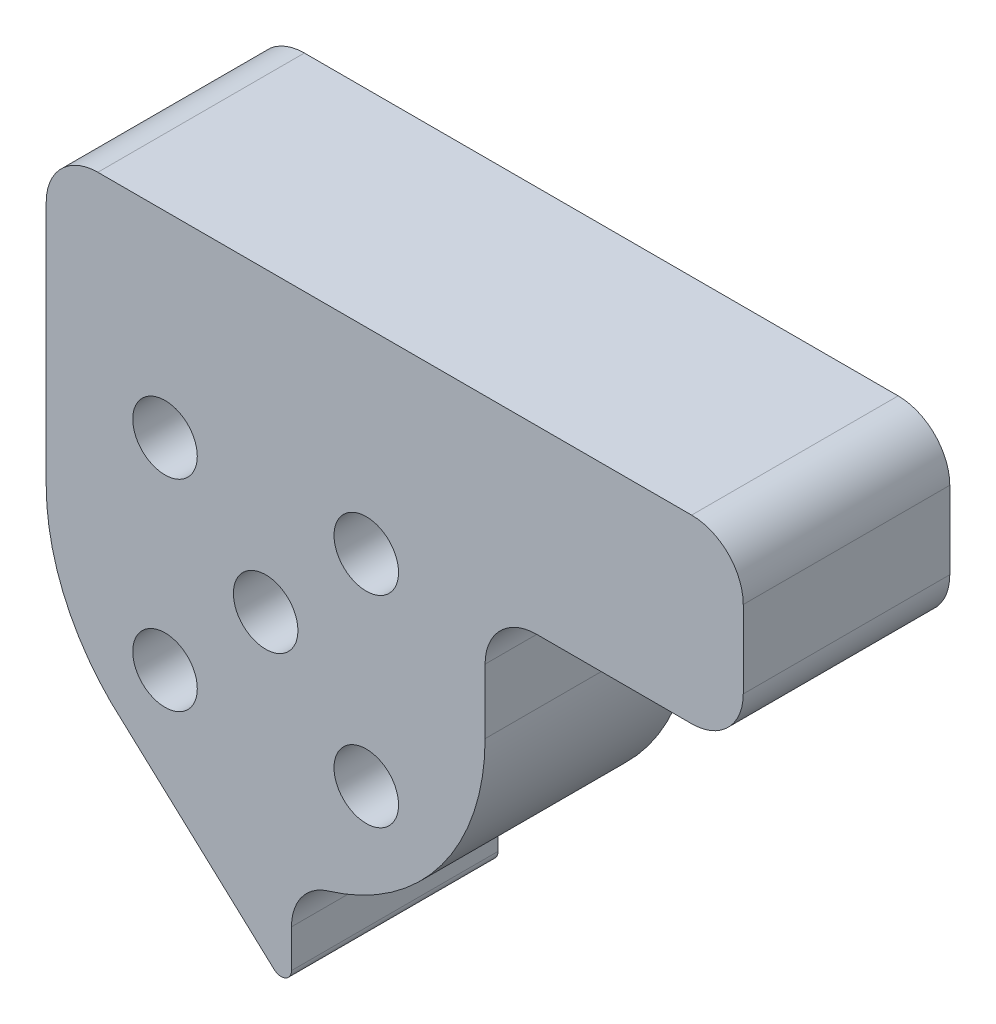
SolidWorks part; units mm, degrees
ref_plane "Front Plane" through (0, 0, 0) normal (0, 0, 1) x (1, 0, 0)
ref_plane "Top Plane" through (0, 0, 0) normal (0, 1, 0) x (1, 0, 0)
ref_plane "Right Plane" through (0, 0, 0) normal (1, 0, 0) x (0, 0, -1)
sketch "Sketch1" plane through (0, 0, 0) normal (0, 0, 1) x (1, 0, 0)
  line L0 (10.795, 0) -> (10.795, 5.715)
  line L1 (-4.95, 4.95) -> (4.95, 4.95) construction
  line L2 (-4.95, 4.95) -> (-4.95, -4.95) construction
  line L3 (-4.95, -4.95) -> (4.95, -4.95) construction
  line L4 (4.95, 4.95) -> (4.95, -4.95) construction
  line L5 (-4.95, 4.95) -> (4.95, -4.95) construction
  line L6 (-4.95, -4.95) -> (4.95, 4.95) construction
  line L7 (10.795, 10.795) -> (23.495, 10.795) construction
  line L8 (23.495, 10.795) -> (23.495, 14.605)
  line L9 (23.495, 14.605) -> (-10.795, 14.605)
  line L10 (-10.795, 14.605) -> (-10.795, 0)
  line L11 (1.27, -10.72) -> (1.27, -15.8)
  line L12 (1.27, -15.8) -> (-7.62, -7.6464)
  line L13 (23.495, 10.795) -> (23.495, 5.715)
  line L14 (23.495, 5.715) -> (10.795, 5.715)
  line L15 (10.795, 5.715) -> (10.795, 10.795) construction
  circle A0 centre (0, 0) radius 1.5875
  circle A1 centre (-4.95, 4.95) radius 1.5875
  circle A2 centre (-4.95, -4.95) radius 1.5875
  circle A3 centre (4.95, -4.95) radius 1.5875
  circle A4 centre (4.95, 4.95) radius 1.5875
  arc A5 (-10.795, 0) -> (-7.62, -7.6464) centre (0, 0) ccw
  arc A6 (10.795, 0) -> (-10.795, 0) centre (0, 0) ccw construction
  arc A7 (-7.62, -7.6464) -> (1.27, -10.72) centre (0, 0) ccw construction
  arc A8 (1.27, -10.72) -> (10.795, 0) centre (0, 0) ccw
  point P0 (0, 0)
  dimension "D3" = 3.175
  dimension "D4" = 21.59
  dimension "D1" = 9.9
  dimension "D2" = 9.9
  dimension "D5" = 12.7
  dimension "D6" = 3.81
  dimension "D7" = 1.27
  dimension "D8" = 5.08
  dimension "D9" = 7.62
  dimension "D10" = 5.08
extrude "Boss-Extrude1" add sketch "Sketch1" along normal blind 10.16
fillet "Fillet1" radius 2.54 5 edges at (23.495, 5.715, 5.08) (23.495, 14.605, 5.08) (-10.795, 14.605, 5.08) (1.27, -10.72, 5.08) (10.795, 5.715, 5.08)
fillet "Fillet2" radius 0.508 1 edges at (1.27, -15.8, 5.08)
